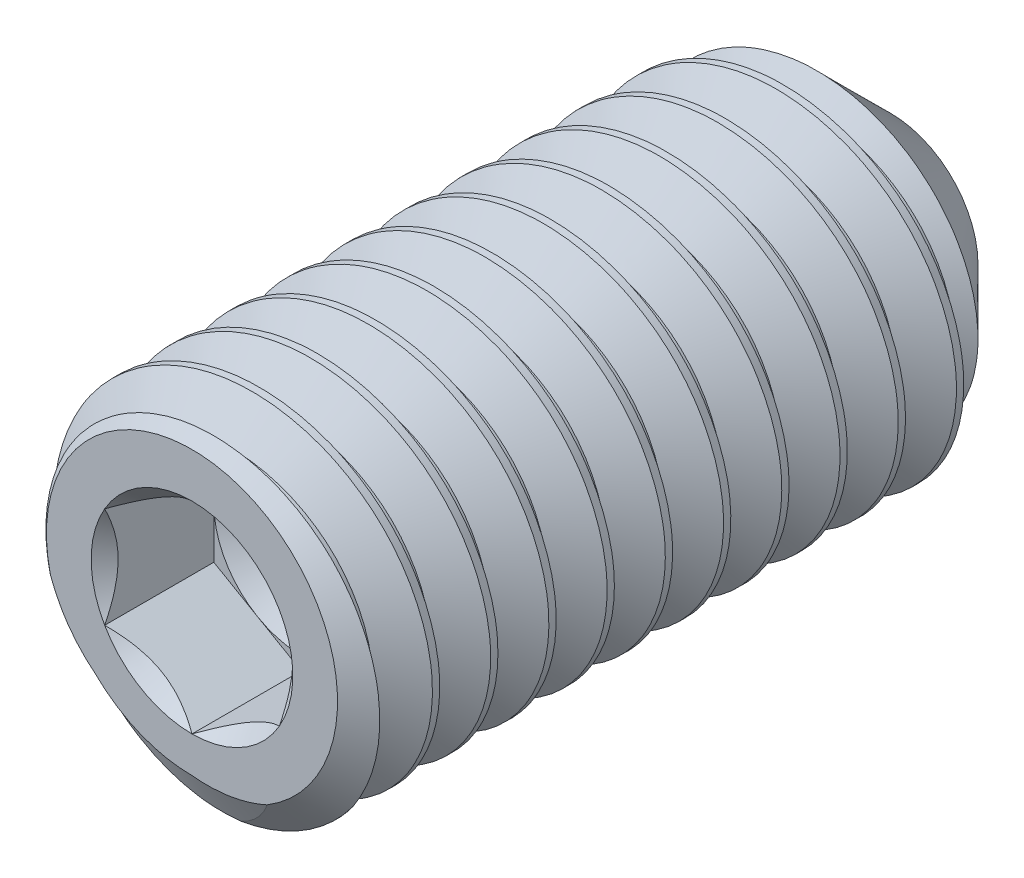
SolidWorks part; units mm, degrees
other "Imported1" parameters "D3"=6.6, "D1"=46.842, "Length"=6, "Drive Size"=1.5, "Thread Size"=3, "Thread Pitch"=0.5, "hex Depth"=0.9375, "D2"=0.9112, "Dia"=12, "D4"=2.3829, "Cup Point Dia"=3.3528, "D5"=1.436, "D6"=1.4986, "D7"=5.0014, "Pitch"=1.75
ref_plane "Front" through (0, 0, 0) normal (0, 0, 1) x (1, 0, 0)
ref_plane "Top" through (0, 0, 0) normal (0, 1, 0) x (1, 0, 0)
ref_plane "Right" through (0, 0, 0) normal (1, 0, 0) x (0, 0, -1)
sketch "Sketch1" plane through (0, 0, 0) normal (1, 0, 0) x (0, 0, -1)
  line L0 (3, 1.5) -> (-3, 1.5) construction
  line L1 (-3, 1.5) -> (-3, -1.5) construction
  line L2 (-3, -1.5) -> (3, -1.5) construction
  line L3 (3, -1.5) -> (3, 1.5) construction
  line L4 (-3, 0.75) -> (-3, -0.75) construction
  line L5 (2.9688, 1.5541) -> (3.4688, 1.5541) construction
  line L6 (3.4688, 1.5541) -> (3.2188, 1.1211) construction
  line L7 (3.2188, 1.1211) -> (2.9688, 1.5541) construction
  line L8 (2.9844, 1.5271) -> (3.4531, 1.5271) construction
  line L9 (3, 1.5) -> (3.4375, 1.5) construction
  line L10 (3.2188, 1.5541) -> (3.2188, 1.5) construction
  line L11 (3.1875, 1.1752) -> (3.25, 1.1752) construction
  line L12 (3.2188, 1.1752) -> (3.2188, 1.1211) construction
  point P3 (0, 1.5)
  point P19 (3.2188, 1.5271)
  point P24 (-3, 0)
  point P25 (-3, 0)
  dimension "D1" = 0.0625
sketch "Sketch11" plane through (0, 0, 0) normal (1, 0, 0) x (0, 0, -1)
  line L0 (-3, 0) -> (-3, 1.25)
  line L1 (-3, 1.25) -> (-2.8249, 1.5)
  line L2 (-2.8249, 1.5) -> (2.25, 1.5)
  line L3 (2.25, 1.5) -> (3, 0.75)
  line L4 (3, 0.75) -> (2.5494, 0)
  line L5 (2.5494, 0) -> (-3, 0)
  line L6 (2.5494, 0) -> (3, 0) construction
  line L7 (3, 0) -> (3, 0.75) construction
  line L8 (3, -0.75) -> (2.5494, 0) construction
  line L9 (-2.8249, -1.5) -> (2.25, -1.5) construction
  line L10 (-3, -1.5) -> (3, -1.5) construction
  line L11 (-3, 1.5) -> (-3, -1.5) construction
  line L12 (3, -1.5) -> (3, 1.5) construction
  point P11 (1.25, -1.5)
  point P12 (-3, 1.5)
  dimension "D3" = 35
  dimension "D5" = 118
  dimension "D6" = 45
  dimension "D1" = 0.25
  dimension "D2" = 1.75
  dimension "D4" = 0.75
revolve "Revolve1" add sketch "Sketch11" angle 360 about L6
sketch "Sketch2" plane through (0, 0, 3) normal (0, 0, 1) x (1, 0, 0)
  line L1 (0, 0.866) -> (-0.75, 0.433)
  line L2 (-0.75, 0.433) -> (-0.75, -0.433)
  line L3 (-0.75, -0.433) -> (0, -0.866)
  line L4 (0, -0.866) -> (0.75, -0.433)
  line L5 (0.75, -0.433) -> (0.75, 0.433)
  line L6 (0.75, 0.433) -> (0, 0.866)
  circle A0 centre (0, 0) radius 0.75 construction
  circle A1 centre (0, 0) radius 1.5 construction
extrude "Cut-Extrude1" cut sketch "Sketch2" against normal blind 0.9375
sketch "Sketch3" plane through (0, 0, 3) normal (0, 0, 1) x (1, 0, 0)
  circle A0 centre (0, 0) radius 0.866
extrude "Cut-Extrude2" cut sketch "Sketch3" against normal through all draft 45
sketch "Sketch4" plane through (0, 0, 2.0625) normal (0, 0, 1) x (1, 0, 0)
  circle A0 centre (0, 0) radius 0.75 construction
  circle A1 centre (0, 0) radius 0.75
extrude "Cut-Extrude3" cut sketch "Sketch4" against normal through all draft 60
sketch "Sketch13" plane through (0, 0, 0) normal (1, 0, 0) x (0, 0, -1)
  line L0 (0, -1.5) -> (0, 1.5) construction
  line L2 (-2.8249, 1.5) -> (2.25, 1.5) construction
  line L4 (2.5494, 0) -> (-3, 0) construction
  point P0 (-0.4506, 0)
  point P4 (0, 0)
  point P9 (0.4506, 0)
  dimension "D1" = 3
ref_plane "Plane1" through (0, 0, -3) normal (0, 0, 1) x (1, 0, 0)
sketch "Sketch5" plane through (0, 0, -3) normal (0, 0, 1) x (1, 0, 0)
  circle A0 centre (0, 0) radius 1.5 construction
  circle A1 centre (0, 0) radius 1.5
curve "Helix/Spiral1" pitch 0.5 height 6.6 radius 1.5 centre (0, 0, -3) axis (0, 0, 1) start towards (0, 1, 0)
sketch "Sketch6" plane through (0, 0, 0) normal (1, 0, 0) x (0, 0, -1)
  line L0 (2.9687, 1.5541) -> (3.4687, 1.5541) construction
  line L1 (3.4687, 1.5541) -> (3.2188, 1.1211) construction
  line L2 (3.2188, 1.1211) -> (2.9687, 1.5541) construction
  line L3 (3.2188, 1.5541) -> (3.2187, 1.5) construction
  line L4 (3, 1.5) -> (3.4375, 1.5) construction
  line L5 (3.2187, 1.1752) -> (3.2188, 1.1211) construction
  line L6 (3.1875, 1.1752) -> (2.9844, 1.5271)
  line L7 (2.9844, 1.5271) -> (3.4531, 1.5271)
  line L8 (2.9844, 1.5271) -> (3.4531, 1.5271) construction
  line L10 (3.1875, 1.1752) -> (3.25, 1.1752) construction
  line L12 (3.25, 1.1752) -> (3.1875, 1.1752)
  line L13 (3.4531, 1.5271) -> (3.25, 1.1752)
  point P9 (3.2187, 1.5)
  point P14 (3.2188, 1.5271)
  point P15 (3.2188, 1.5271)
  point P16 (3.2187, 1.1752)
  dimension "D1" = 0.5
  dimension "D2" = 0.0625
sweep "Cut-Sweep1" cut profiles "Sketch6" path "Helix/Spiral1"
equation "\"D3@Helix/Spiral1\" = \"Length@Sketch1\" * 1.1"
equation "\"hex Depth@Cut-Extrude1\" = \"Drive Size@Sketch1\" * .625"
equation "\"D1@Sketch6\" = \"Thread Pitch@Sketch1\""
equation "\"D2@Sketch6\" = \"D1@Sketch6\" / 8"
equation "\"D1@Sketch11\" = \"Thread Pitch@Sketch1\" * .5"
equation "\"D2@Sketch11\" = \"Thread Pitch@Sketch1\" * 3.5"
equation "\"D1@Helix/Spiral1\" = \"Thread Pitch@Sketch1\""
equation "\"D4@Sketch11\" = \"Thread Pitch@Sketch1\" * 1.5"
equation "\"D1@Sketch1\" = \"Thread Pitch@Sketch1\" / 8"
equation "\"D1@Sketch13\"=\"Thread Size@Sketch1\""
